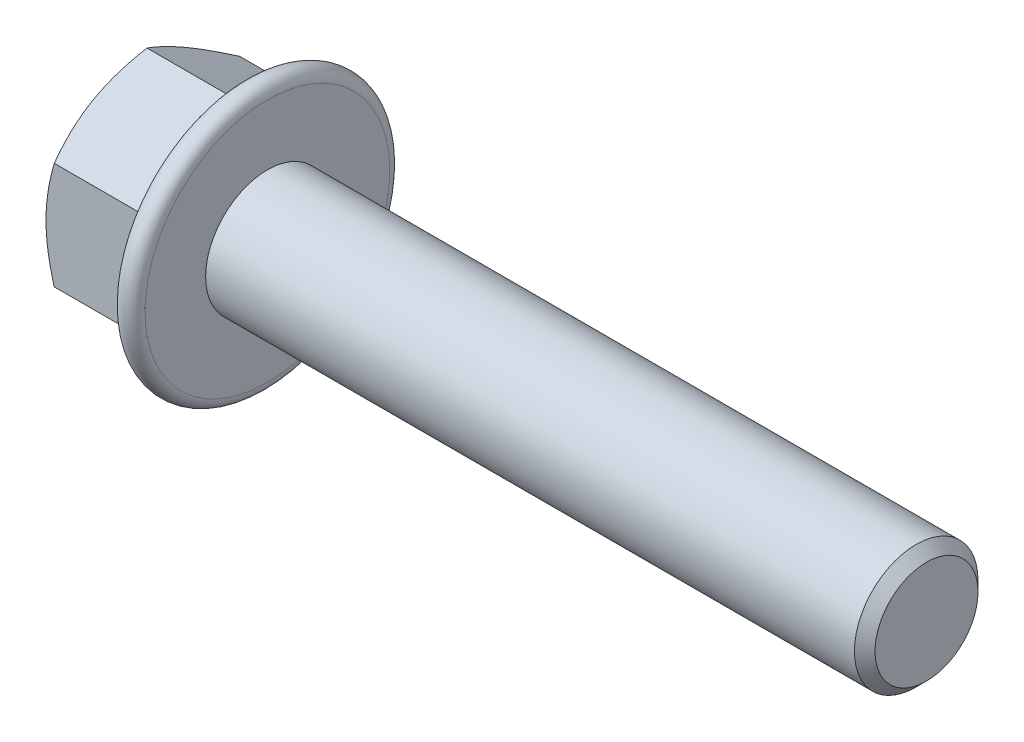
SolidWorks part; units mm, degrees
material "Alloy Steel"
ref_plane "Front Plane" through (0, 0, 0) normal (0, 0, 1) x (1, 0, 0)
ref_plane "Top Plane" through (0, 0, 0) normal (0, 1, 0) x (1, 0, 0)
ref_plane "Right Plane" through (0, 0, 0) normal (1, 0, 0) x (0, 0, -1)
sketch "Sketch1" plane through (0, 0, 0) normal (0, 0, 1) x (1, 0, 0)
  line L0 (0, 0) -> (50.8, 0) construction
  line L1 (0, 0) -> (-9.9219, 0) construction
  line L2 (0, 10.3187) -> (0, -10.3187) construction
  line L3 (-9.9219, 7.1437) -> (-9.9219, -7.1438) construction
  line L4 (50.8, 4.7625) -> (50.8, -4.7625) construction
  point P8 (25.4, 0)
  point P11 (47.0958, -4.7625)
  dimension "D1" = 3.7042
sketch "Sketch2" plane through (0, 0, 0) normal (1, 0, 0) x (0, 0, -1)
  circle A0 centre (0, 0) radius 4.7625
extrude "Boss-Extrude1" add sketch "Sketch2" along normal up to vertex (50.8 mm away) up to point (50.8, 4.7625, 0)
chamfer "Chamfer1" distance 0.7938 angle 45 1 edges at (50.8, 0, -4.7625)
sketch "Sketch12" plane through (50.8, 0, 0) normal (1, 0, 0) x (0, 0, -1)
  circle A0 centre (0, 0) radius 4.7625 construction
  circle A1 centre (0, 0) radius 4.7625
curve "Helix/Spiral2" [suppressed] parameters "Pitch"=1.0583
sketch "Sketch13" plane through (0, 0, 0) normal (0, 0, 1) x (1, 0, 0)
  line L0 (50.8, 4.7625) -> (51.1969, 4.0751)
  line L1 (51.1969, 4.0751) -> (51.3292, 4.0751)
  line L2 (51.3292, 4.0751) -> (51.726, 4.7625)
  line L3 (51.726, 4.7625) -> (50.8, 4.7625)
  line L4 (51.263, 4.7625) -> (51.263, 4.0751) construction
  line L5 (50.9984, 4.4188) -> (51.5276, 4.4188) construction
  line L6 (50.8, -4.7625) -> (50.8, 4.7625) construction
  dimension "D1" = 60
  dimension "D2" = 0.5292
  dimension "D3" = 0.1323
sweep "Cut-Sweep1" [suppressed] cut profiles "Sketch13" path "Helix/Spiral2"
ref_plane "Plane1" through (25.4, 0, 0) normal (1, 0, 0) x (0, 0, -1)
sketch "Sketch3" plane through (0, 0, 0) normal (-1, 0, 0) x (0, 0, 1)
  line L0 (0, 8.2489) -> (0, 0) construction
  line L1 (0, 8.2489) -> (-7.1438, 4.1244)
  line L2 (-7.1438, 4.1244) -> (-7.1437, -4.1244)
  line L3 (-7.1437, -4.1244) -> (0, -8.2489)
  line L4 (0, -8.2489) -> (7.1437, -4.1244)
  line L5 (7.1437, -4.1244) -> (7.1437, 4.1244)
  line L6 (7.1437, 4.1244) -> (0, 8.2489)
  circle A0 centre (0, 0) radius 7.1437 construction
extrude "Boss-Extrude2" add sketch "Sketch3" along normal up to vertex (9.9219 mm away) up to point (-9.9219, 7.1437, 0)
sketch "Sketch4" plane through (0, 0, 0) normal (0, 0, 1) x (1, 0, 0)
  line L0 (0, 0) -> (0, 9.4326)
  line L1 (-0.8862, 10.3187) -> (0, 10.3187) construction
  line L2 (-1.6536, 9.8757) -> (-3.2309, 7.1437)
  line L3 (-3.2309, 7.1437) -> (-3.2309, 0)
  line L4 (0, 0) -> (-9.9219, 0) construction
  line L5 (-3.2309, 0) -> (0, 0)
  line L6 (-9.9219, 7.1437) -> (-3.2309, 7.1437) construction
  arc A0 (0, 9.4326) -> (-1.6536, 9.8757) centre (-0.8862, 9.4326) ccw
  dimension "D1" = 30
  dimension "D2" = 1.6536
revolve "Revolve1" add sketch "Sketch4" angle 360 about L5
sketch "Sketch5" plane through (-9.9219, 0, 0) normal (-1, 0, 0) x (0, 0, 1)
  circle A0 centre (0, 0) radius 7.1437 construction
  circle A1 centre (0, 0) radius 7.1437
extrude "Cut-Extrude1" cut sketch "Sketch5" against normal up to vertex (9.9219 mm away) draft 60 flip side to cut up to point (0, 0, 0)
sketch "Sketch6" plane through (-9.9219, 0, 0) normal (-1, 0, 0) x (0, 0, 1)
  line L0 (0, 7.1437) -> (0, -7.1438) construction
  circle A0 centre (0, 0) radius 6.4294
  dimension "D1" = 12.8587
extrude "Cut-Extrude2" cut sketch "Sketch6" against normal blind 0.8268 draft 35
sketch "Sketch11" plane through (-9.0951, 0, 0) normal (-1, 0, 0) x (0, 0, 1)
  line L0 (0, 5.5007) -> (0, 1.9288) construction
  line L1 (0.2143, 5.5007) -> (0.2143, 1.9288)
  line L2 (-0.2143, 5.5007) -> (-0.2143, 1.9288)
  arc A0 (0.2143, 5.5007) -> (-0.2143, 5.5007) centre (0, 5.5007) ccw
  arc A1 (-0.2143, 1.9288) -> (0.2143, 1.9288) centre (0, 1.9288) ccw
  circle A2 centre (0, 0) radius 5.715 construction
  circle A3 centre (0, 0) radius 1.7145 construction
  point P3 (0, 3.7147)
  dimension "D1" = 11.43
  dimension "D2" = 3.429
  dimension "D3" = 0.4286
extrude "Cut-Extrude3" [suppressed] cut sketch "Sketch11" against normal blind 0.254
pattern_circular "CirPattern1" [suppressed] count 6 over 360 of bodies 115
sketch "Sketch14" plane through (0, 0, 0) normal (0, 0, 1) x (1, 0, 0)
  line L0 (0, 4.7625) -> (0, 0)
  line L1 (0, 0) -> (25.4, 0)
  line L2 (25.4, 0) -> (25.4, 4.7625)
  line L3 (25.4, 4.7625) -> (0, 4.7625)
revolve "Revolve2" add sketch "Sketch14" angle 360 mid plane about L1
move or copy body "Body-Move/Copy1" [suppressed] bodies to move or copy 117
equation "\"D2@Sketch4\" = \"Head Ht.@Sketch1\" / 6"
equation "\"D1@Sketch6\" = \"Head Wd.@Sketch1\" * 0.9"
equation "\"D1@Cut-Extrude2\" = \"D2@Sketch4\" / 2"
equation "\"D1@Sketch11\" = \"Head Wd.@Sketch1\"*.8"
equation "\"D2@Sketch11\" = \"D1@Sketch11\"*.3"
equation "\"D3@Sketch11\" = \"Head Wd.@Sketch1\"*.03"
equation "\"D2@Sketch13\" = \"Pitch@Helix/Spiral2\"*.50"
equation "\"D3@Sketch13\" = \"Pitch@Helix/Spiral2\"*.125"
equation "\"D3@Helix/Spiral2\" = \"Lg.@Sketch1\"+\"Pitch@Helix/Spiral2\""
equation "\"D1@Chamfer1\" = \"Pitch@Helix/Spiral2\"*.750"
equation "\"D1@Sketch1\" = \"Pitch@Helix/Spiral2\"*3.50"
